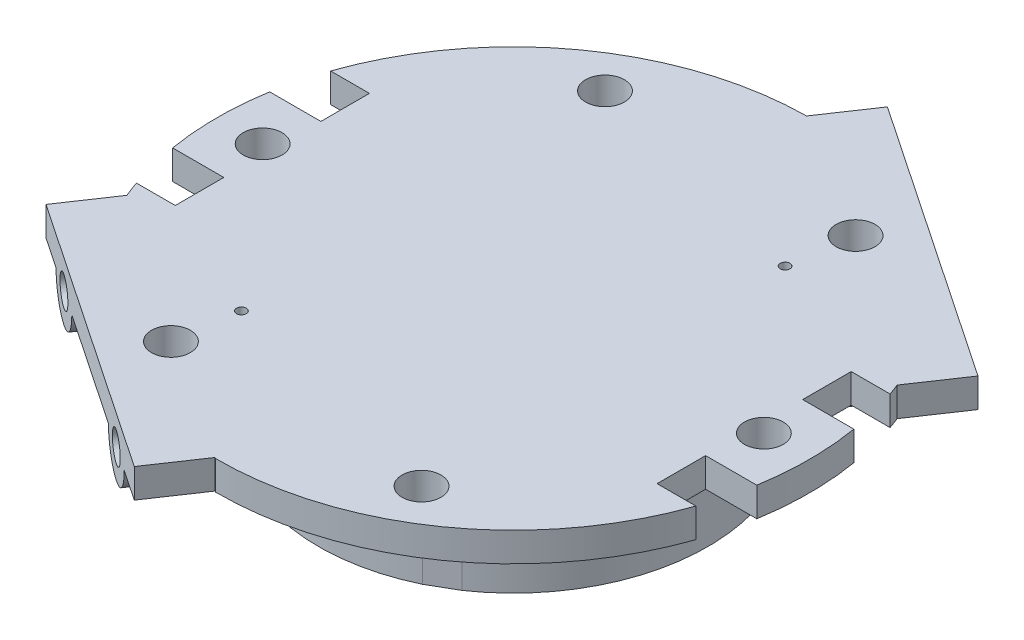
SolidWorks part; units mm, degrees
ref_plane "Alzado" through (0, 0, 0) normal (0, 0, 1) x (1, 0, 0)
ref_plane "Planta" through (0, 0, 0) normal (0, 1, 0) x (1, 0, 0)
ref_plane "Vista lateral" through (0, 0, 0) normal (1, 0, 0) x (0, 0, -1)
sketch "Croquis1" plane through (0, 0, 0) normal (0, 1, 0) x (1, 0, 0)
  circle A0 centre (0, 0) radius 30.5
extrude "Saliente-Extruir1" add sketch "Croquis1" along normal blind 3
sketch "Croquis5" plane through (0, 3, 0) normal (0, 1, 0) x (1, 0, 0)
  line L1 (28.8141, -5) -> (30.0874, -5)
  line L2 (28.8141, 5) -> (30.0874, 5)
  line L3 (-24.8141, 10) -> (-28.8141, 10)
  line L4 (24.8141, -5) -> (24.8141, -10)
  line L5 (-24.8141, -10) -> (-28.8141, -10)
  line L6 (24.8141, -5) -> (28.8141, -5)
  line L7 (24.8141, 5) -> (24.8141, 10)
  line L8 (-24.8141, 5) -> (-28.8141, 5)
  line L9 (-24.8141, 5) -> (-24.8141, 10)
  line L10 (-24.8141, -5) -> (-28.8141, -5)
  line L11 (-24.8141, -5) -> (-24.8141, -10)
  line L12 (24.8141, 5) -> (28.8141, 5)
  line L13 (24.8141, -10) -> (28.8141, -10)
  line L14 (24.8141, 10) -> (28.8141, 10)
  line L15 (-28.8141, 5) -> (-30.0874, 5)
  line L16 (-28.8141, -5) -> (-30.0874, -5)
  line L18 (-24.8141, 0) -> (-12.407, -21.4896)
  line L19 (-12.407, -21.4896) -> (12.407, -21.4896)
  line L20 (12.407, -21.4896) -> (24.8141, 0)
  line L21 (24.8141, 0) -> (12.407, 21.4896)
  line L22 (12.407, 21.4896) -> (-12.407, 21.4896)
  line L23 (-12.407, 21.4896) -> (-24.8141, 0)
  circle A0 centre (0, 0) radius 21.4896 construction
  circle A1 centre (0, 0) radius 30.5 construction
  arc A2 (-28.8141, 10) -> (-30.0874, 5) centre (0, 0) ccw
  arc A4 (-30.0874, -5) -> (-28.8141, -10) centre (0, 0) ccw
  arc A5 (30.0874, -5) -> (28.8141, -10) centre (0, 0) cw
  arc A6 (28.8141, 10) -> (30.0874, 5) centre (0, 0) cw
  circle M2 centre (0, 0) radius 30.5
extrude "Cortar-Extruir3" cut sketch "Croquis5" against normal blind 4 contours L10 L16 L5 L11 M2 | L15 L8 L9 L3 M2 | L14 L7 L12 L2 M2 | L4 L13 L1 L6 M2 region at (27.1844, 3, 7.3876) region at (-27.1844, 3, 7.3876) region at (27.1844, 3, -7.3876) region at (-27.1844, 3, -7.3876)
sketch "Croquis7" plane through (0, 3, 0) normal (0, 1, 0) x (1, 0, 0)
  line L2 (25.8141, 0) -> (12.907, 22.3556)
  line L3 (12.907, 22.3556) -> (-12.907, 22.3556)
  line L4 (-12.907, 22.3556) -> (-25.8141, 0)
  line L5 (-25.8141, 0) -> (-12.907, -22.3556)
  line L6 (-12.907, -22.3556) -> (12.907, -22.3556)
  line L7 (12.907, -22.3556) -> (25.8141, 0)
  circle A0 centre (25.8141, 0) radius 2
  circle A4 centre (-25.8141, 0) radius 2
  circle A5 centre (0, 0) radius 22.3556 construction
  circle A6 centre (12.907, 22.3556) radius 2
  circle A7 centre (-12.907, -22.3556) radius 2
  circle A8 centre (-12.907, 22.3556) radius 2
  circle A9 centre (12.907, -22.3556) radius 2
extrude "Cortar-Extruir4" cut sketch "Croquis7" against normal blind 10 contours A8 L4 L3 | A4 L4 L5 | A4 L5 L4 | A8 L3 L4 | L2 A6 L3 | L3 A6 L2 | L7 A0 L2 | L2 A0 L7 | A7 L5 L6 | A7 L6 L5 | L6 A9 L7 | L7 A9 L6 | A4 region at (24.7114, 3, 0) region at (26.3654, 3, 0) region at (12.3557, 3, -21.4007) region at (13.1827, 3, -22.8331) region at (13.1827, 3, 22.8331) region at (12.3557, 3, 21.4007) region at (-12.3557, 3, -21.4007) region at (-13.1827, 3, -22.8331) region at (-13.1827, 3, 22.8331) region at (-12.3557, 3, 21.4007) region at (-24.7114, 3, 0) region at (-26.3654, 3, 0)
sketch "Croquis8" plane through (0, 3, 0) normal (0, 1, 0) x (1, 0, 0)
  line L0 (0, 0) -> (12, 0)
  line L1 (12, 0) -> (12, 16)
  line L2 (0, 0) -> (-12, 0)
  line L3 (-12, 0) -> (-12, -16)
  circle A0 centre (12, 16) radius 0.5
  circle A1 centre (-12, -16) radius 0.5
extrude "Cortar-Extruir5" cut sketch "Croquis8" against normal blind 3 contours A1 | A0 region at (11.6564, 3, -16.3436) region at (-11.6564, 3, 15.6564)
sketch "Croquis9" plane through (0, 3, 0) normal (0, 1, 0) x (1, 0, 0)
  line L2 (-10, 17.3205) -> (-8.701, 18.0705)
  line L5 (25.6318, 16.5306) -> (27.1318, 13.9325)
  line L6 (-10, 17.3205) -> (-11.299, 16.5705)
  line L8 (10, -17.3205) -> (8.701, -18.0705)
  line L9 (10, -17.3205) -> (11.299, -16.5705)
  circle A0 centre (0, 0) radius 20.0562
  circle A1 centre (-12, -16) radius 3
  circle A2 centre (12, 16) radius 3
extrude "Saliente-Extruir2" add sketch "Croquis9" against normal blind 13 contours L2 L6 | L8 L9 region at (0, 3, 0)
sketch "Croquis10" plane through (0, 3, 0) normal (0, 1, 0) x (1, 0, 0)
  line L3 (29.8013, 10.2046) -> (-1.7022, 31.454)
  circle A0 centre (0, 0) radius 31.5
extrude "Cortar-Extruir6" cut sketch "Croquis10" against normal blind 3 contours L3 A0 rebuild error yes
sketch "Croquis11" plane through (14.0495, 0, -20.8293) normal (0.5592, 0, -0.829) x (-0.829, 0, -0.5592)
  line L1 (17.2916, 0) -> (-17.2916, 0)
  line L2 (17.2916, 0) -> (17.2916, 3)
  line L3 (17.2916, 3) -> (-17.2916, 3)
  line L4 (-17.2916, 0) -> (-17.2916, 3)
extrude "Saliente-Extruir3" add sketch "Croquis11" along normal blind 6
sketch "Croquis12" plane through (0, 3, 0) normal (0, 1, 0) x (1, 0, 0)
  circle A0 centre (12.907, 22.3556) radius 2
extrude "Cortar-Extruir7" cut sketch "Croquis12" against normal blind 3
sketch "Croquis13" plane through (17.4047, 0, -25.8035) normal (0.5592, 0, -0.829) x (-0.829, 0, -0.5592)
  line L0 (-17.2916, 0) -> (17.2916, 0)
  line L1 (17.2916, 3) -> (-17.2916, 3)
  line L2 (17.2916, 3) -> (-17.2916, 3) construction
  line L3 (17.2916, 0) -> (17.2916, 3) construction
  circle A1 centre (10, 0) radius 3
  circle A2 centre (-10, 0) radius 3
  circle A3 centre (10, 0) radius 1.5
  circle A5 centre (-10, 0) radius 1.5
  line M4 (-17.2916, 0) -> (17.2916, 0)
extrude "Saliente-Extruir4" add sketch "Croquis13" against normal blind 20 contours A3 L0 A1 | A3 L0 A1 | A5 L0 A2 | A5 L0 A2 | A5 M4 | A3 M4 region at (25.6951, 1.5671, -20.2116) region at (25.6951, -0.6366, -20.2116) region at (23.8297, -0.0671, -21.4698) region at (10.8337, 2.0739, -30.2358) region at (10.9797, -0.0671, -30.1373) region at (9.1143, -0.6366, -31.3955)
sketch "Croquis14" plane through (17.4047, 0, -25.8035) normal (0.5592, 0, -0.829) x (-0.829, 0, -0.5592)
  circle A0 centre (-10, 0) radius 1.5
  circle A1 centre (10, 0) radius 1.5
extrude "Cortar-Extruir8" cut sketch "Croquis14" against normal blind 5
sketch "Croquis15" plane through (0, 3, 0) normal (0, 1, 0) x (1, 0, 0)
  line L0 (28.3849, 11.16) -> (-0.2859, 30.4987)
  line L1 (28.3849, 11.16) -> (0.1409, -30.7136)
  line L2 (-0.2859, 30.4987) -> (-28.5299, -11.3749)
  line L3 (0.1409, -30.7136) -> (-28.5299, -11.3749)
  circle A0 centre (-0.2859, 0) radius 30.7165
  arc M12 (-28.8141, -10) -> (28.8141, -10) centre (0, 0) ccw
  circle M28 centre (-12.907, -22.3556) radius 2
extrude "Cortar-Extruir9" cut sketch "Croquis15" against normal blind 3 contours L3 M12 M28 region at (-15.494, 3, 22.7434)
sketch "Croquis16" plane through (-14.1945, 0, 21.0442) normal (-0.5592, 0, 0.829) x (0.829, 0, 0.5592)
  line L0 (-16.9088, 0) -> (-16.9088, 3)
  line L1 (-16.9088, 0) -> (16.78, 0)
  line L2 (-16.9088, 3) -> (16.78, 3)
  line L3 (16.78, 0) -> (16.78, 3)
extrude "Saliente-Extruir5" add sketch "Croquis16" along normal blind 6
sketch "Croquis17" plane through (0, 3, 0) normal (0, 1, 0) x (1, 0, 0)
  circle A0 centre (-12.907, -22.3556) radius 2
extrude "Cortar-Extruir10" cut sketch "Croquis17" against normal blind 3
sketch "Croquis18" plane through (-17.5497, 0, 26.0185) normal (-0.5592, 0, 0.829) x (0.829, 0, 0.5592)
  line L2 (-16.9088, 0) -> (16.78, 0) construction
  circle A0 centre (9.9356, 0) radius 3
  circle A1 centre (-10.0644, 0) radius 3
extrude "Saliente-Extruir6" add sketch "Croquis18" against normal blind 25
sketch "Croquis19" plane through (-17.5497, 0, 26.0185) normal (-0.5592, 0, 0.829) x (0.829, 0, 0.5592)
  circle A0 centre (-10.0644, 0) radius 1.5
  circle A1 centre (9.9356, 0) radius 1.5
extrude "Cortar-Extruir11" cut sketch "Croquis19" against normal blind 5
